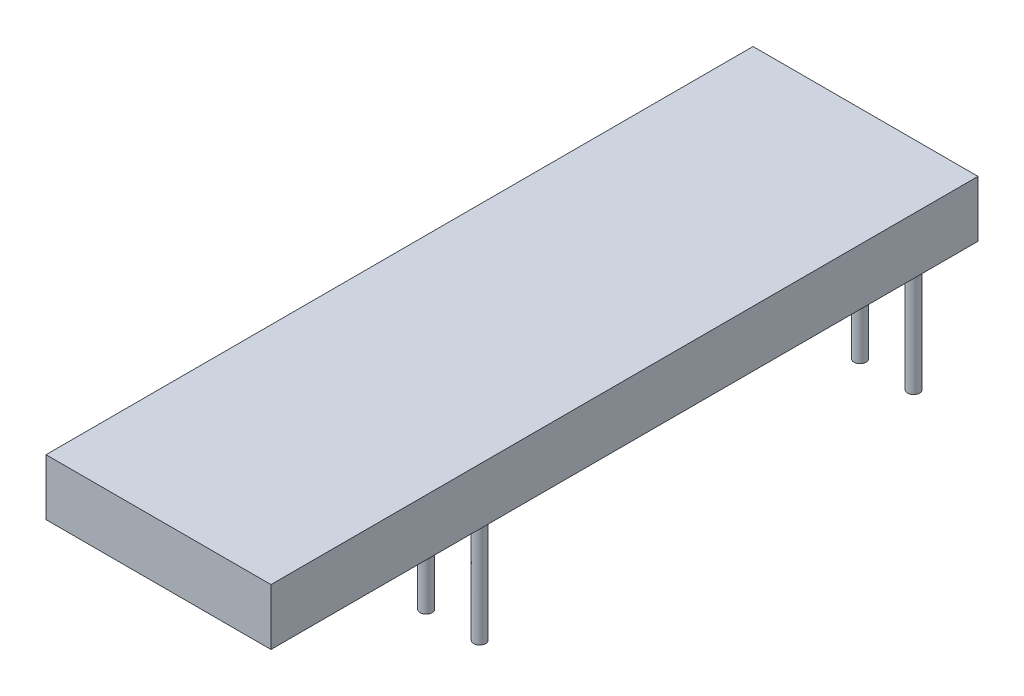
SolidWorks part; units mm, degrees
ref_plane "Front Plane" through (0, 0, 0) normal (0, 0, 1) x (1, 0, 0)
ref_plane "Top Plane" through (0, 0, 0) normal (0, 1, 0) x (1, 0, 0)
ref_plane "Right Plane" through (0, 0, 0) normal (1, 0, 0) x (0, 0, -1)
sketch "Sketch2" plane through (0, 0, 0) normal (0, 1, 0) x (1, 0, 0)
  line L1 (-7, 22) -> (7, 22)
  line L2 (-7, 22) -> (-7, -22)
  line L3 (-7, -22) -> (7, -22)
  line L4 (7, 22) -> (7, -22)
  line L5 (-7, 22) -> (7, -22) construction
  line L6 (-7, -22) -> (7, 22) construction
  point P0 (0, 0)
  dimension "D1" = 14
  dimension "D2" = 44
extrude "Boss-Extrude1" add sketch "Sketch2" along normal blind 3.5
sketch "Sketch3" plane through (0, 3.5, 0) normal (0, 1, 0) x (1, 0, 0)
  line L0 (0, -22) -> (0, 22) construction
  line L1 (-7, -22) -> (7, -22) construction
  line L2 (7, 22) -> (-7, 22) construction
  line L3 (-7, 0) -> (7, 0) construction
  line L4 (-7, 22) -> (-7, -22) construction
  line L5 (7, -22) -> (7, 22) construction
  line L7 (-6.5, -11) -> (6.5, -11)
  line L8 (-6.5, -11) -> (-6.5, -21)
  line L9 (-6.5, -21) -> (6.5, -21)
  line L10 (6.5, -11) -> (6.5, -21)
  line L11 (-6.5, -11) -> (6.5, -21) construction
  line L12 (-6.5, -21) -> (6.5, -11) construction
  point P12 (0, -16)
  dimension "D1" = 1
  dimension "D2" = 0.5
  dimension "D3" = 10
extrude "Boss-Extrude2" [suppressed] add sketch "Sketch3" along normal blind 8
sketch "Sketch4" plane through (0, 0, 0) normal (0, -1, 0) x (1, 0, 0)
  line L0 (7, 7) -> (-7, 7) construction
  line L1 (7, 22) -> (7, -22) construction
  line L2 (-7, -22) -> (-7, 22) construction
  line L3 (-7, 22) -> (7, 22) construction
  circle A0 centre (-5, 7) radius 0.375
  circle A1 centre (-1.67, 7) radius 0.375
  circle A2 centre (1.66, 7) radius 0.375
  circle A3 centre (4.99, 7) radius 0.375
  dimension "D2" = 0.75
  dimension "D3" = 2
  dimension "D5" = 5.33
  dimension "D1" = 15
  dimension "D4" = 4
extrude "Boss-Extrude3" add sketch "Sketch4" along normal blind 8
pattern_linear "LPattern1" count 2 spacing 27 along (0, 0, -1) of "Boss-Extrude3"
